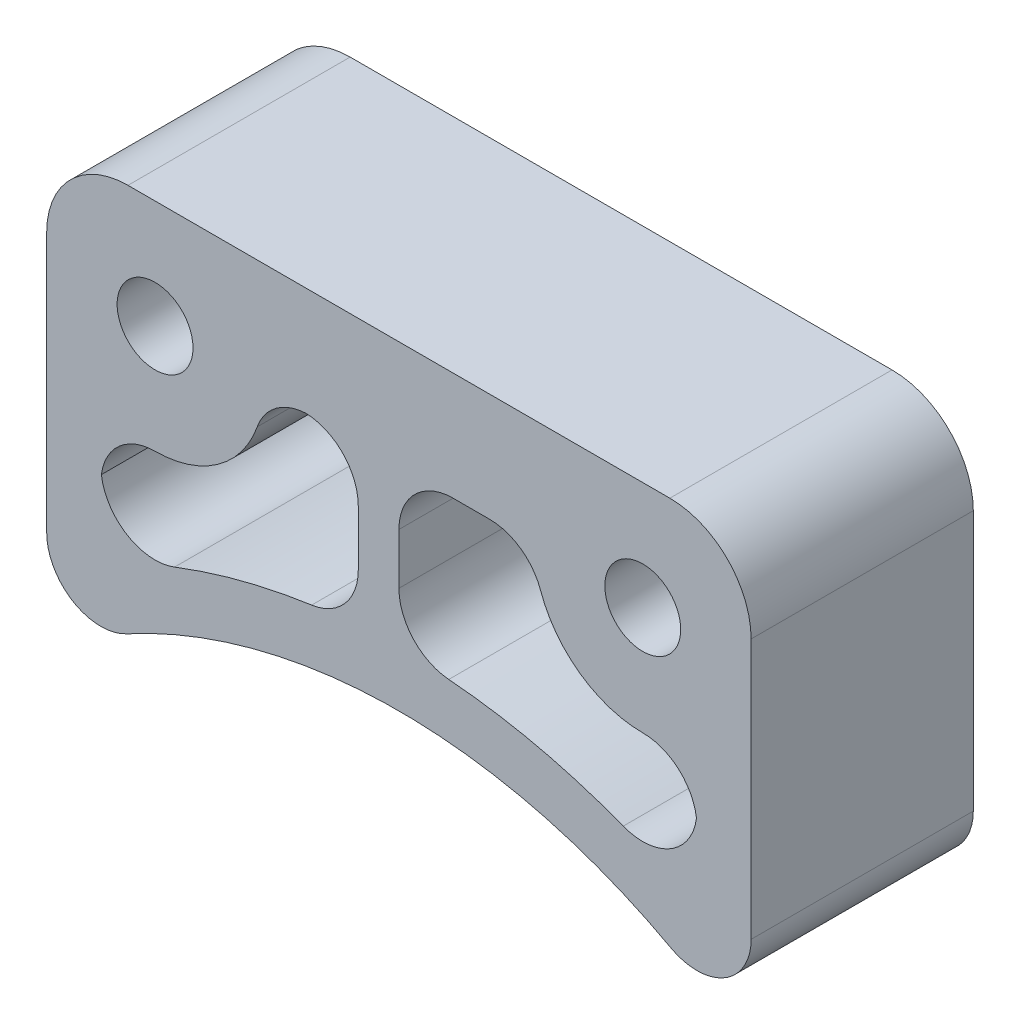
SolidWorks part; units mm, degrees
material "Thornel Mat VMA"
ref_plane "前视基准面" through (0, 0, 0) normal (0, 0, 1) x (1, 0, 0)
ref_plane "上视基准面" through (0, 0, 0) normal (0, 1, 0) x (1, 0, 0)
ref_plane "右视基准面" through (0, 0, 0) normal (1, 0, 0) x (0, 0, -1)
sketch "草图1" plane through (0, 0, 0) normal (0, 0, 1) x (1, 0, 0)
  line L0 (0, 0) -> (-38036.3821, 0) construction
  line L1 (0, 0) -> (0, 38036.3821) construction
  line L2 (-13, 1) -> (-13, -12.3076)
  line L4 (-10, 4) -> (10, 4)
  line L5 (13, 1) -> (13, -12.3076)
  circle A0 centre (-9, 0) radius 1.4
  circle A1 centre (9, 0) radius 1.4
  arc A3 (13, -12.3076) -> (-13, -12.3076) centre (0, -28.8) ccw
  arc A4 (13, 1) -> (10, 4) centre (10, 1) ccw
  arc A5 (-10, 4) -> (-13, 1) centre (-10, 1) ccw
  point P11 (0, -14.8)
  point P13 (0, -14.8)
  point P15 (0, 4)
  point P22 (13, 4)
  point P25 (-13, 4)
  dimension "D1" = 2.8
  dimension "D5" = 3
  dimension "D6" = 21
  dimension "D2" = 18
  dimension "D3" = 4
  dimension "D4" = 4
  dimension "D7" = 14.8
  dimension "D8" = 13.3076
extrude "凸台-拉伸1" add sketch "草图1" along normal blind 8.2
sketch "草图2" plane through (0, 0, 8.2) normal (0, 0, 1) x (1, 0, 0)
  line L0 (-11, -3.4641) -> (-11, -8.601)
  line L1 (-5, 0) -> (5, 0)
  line L2 (0, 0) -> (0, -50000) construction
  line L3 (-13, 1) -> (-13, -12.3076) construction
  line L4 (11, -3.4641) -> (11, -8.601)
  circle A0 centre (-9, 0) radius 4
  circle A1 centre (9, 0) radius 4
  circle A2 centre (0, -28.8) radius 21 construction
  arc A3 (13, -12.3076) -> (-13, -12.3076) centre (0, -28.8) ccw construction
  circle A4 centre (0, -28.8) radius 23
  dimension "D1" = 8
  dimension "D2" = 2
  dimension "D3" = 2
extrude "切除-拉伸1" cut sketch "草图2" against normal blind 10 contours A4 L4 A1 L1 A0 L0 region at (0, -4.0191, 8.2)
sketch "草图3" plane through (0, 0, 8.2) normal (0, 0, 1) x (1, 0, 0)
  line L0 (0, 0) -> (0, -5.8)
  line L1 (-1.5, 0.5796) -> (-1.5, -6.4275)
  line L2 (-1.5, -6.4275) -> (1.5, -6.4275)
  line L3 (1.5, -6.4275) -> (1.5, 0.7514)
  line L4 (1.5, 0.7514) -> (-1.5, 0.5796)
  arc A0 (11, -8.601) -> (-11, -8.601) centre (0, -28.8) ccw construction
  arc M13 (11, -8.601) -> (-11, -8.601) centre (0, -28.8) ccw
  line M16 (-5, 0) -> (5, 0)
  dimension "D1" = 1.5
  dimension "D2" = 1.5
extrude "凸台-拉伸2" add sketch "草图3" against normal up to surface (8.2 mm away) contours L1 L0 M16 M13 region at (-0.7511, -2.9082, 8.2) up to face at (7.6, 0, 0)
fillet "圆角1" radius 2 12 edges at (-11, -8.601, 4.1) (-11, -3.4641, 4.1) (-5, 0, 4.1) (11, -3.4641, 4.1) (11, -8.601, 4.1) (13, -12.3076, 4.1) (-13, -12.3076, 4.1) (5, 0, 4.1) (-1.5, 0, 4.1) (-1.5, -5.849, 4.1) (0, -5.8, 4.1) (0, 0, 4.1)
